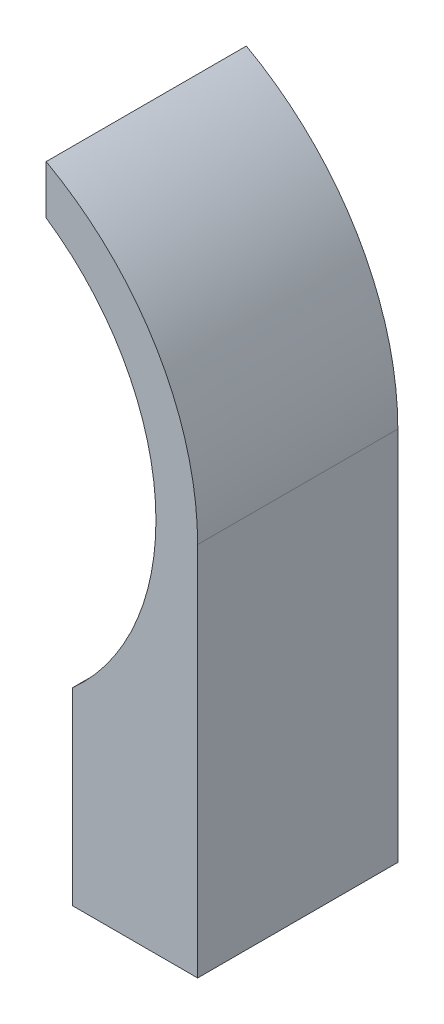
SolidWorks part; units mm, degrees
material "201 Annealed Stainless Steel (SS)"
ref_plane "Front Plane" through (0, 0, 0) normal (0, 0, 1) x (1, 0, 0)
ref_plane "Top Plane" through (0, 0, 0) normal (0, 1, 0) x (1, 0, 0)
ref_plane "Right Plane" through (0, 0, 0) normal (1, 0, 0) x (0, 0, -1)
sketch "Sketch2" plane through (0, 0, 0) normal (0, 0, 1) x (1, 0, 0)
  line L0 (-81.7487, 0) -> (129.7647, 0) construction
  line L1 (0, 82.2046) -> (0, -175) construction
  line L2 (84.2, 0) -> (84.2, 106.5165) construction
  line L3 (100, -111.8034) -> (100, -225)
  line L5 (175, 0) -> (175, -225)
  line L6 (175, -225) -> (100, -225)
  line L7 (84.2, 153.4124) -> (84.2, 124.1385)
  line L8 (0, -175) -> (0, -225) construction
  line L9 (0, -225) -> (111.0903, -225) construction
  line L10 (-100, -111.8034) -> (100, -111.8034) construction
  circle A0 centre (0, 0) radius 150 construction
  circle A1 centre (0, 0) radius 175 construction
  arc A2 (84.2, 124.1385) -> (100, -111.8034) centre (0, 0) cw
  arc A3 (175, 0) -> (84.2, 153.4124) centre (0, 0) ccw
  dimension "D1" = 300
  dimension "D2" = 350
  dimension "D5" = 50
  dimension "D3" = 84.2
  dimension "D6" = 200
extrude "Inner Ring - Right Side" add sketch "Sketch2" along normal blind 120
